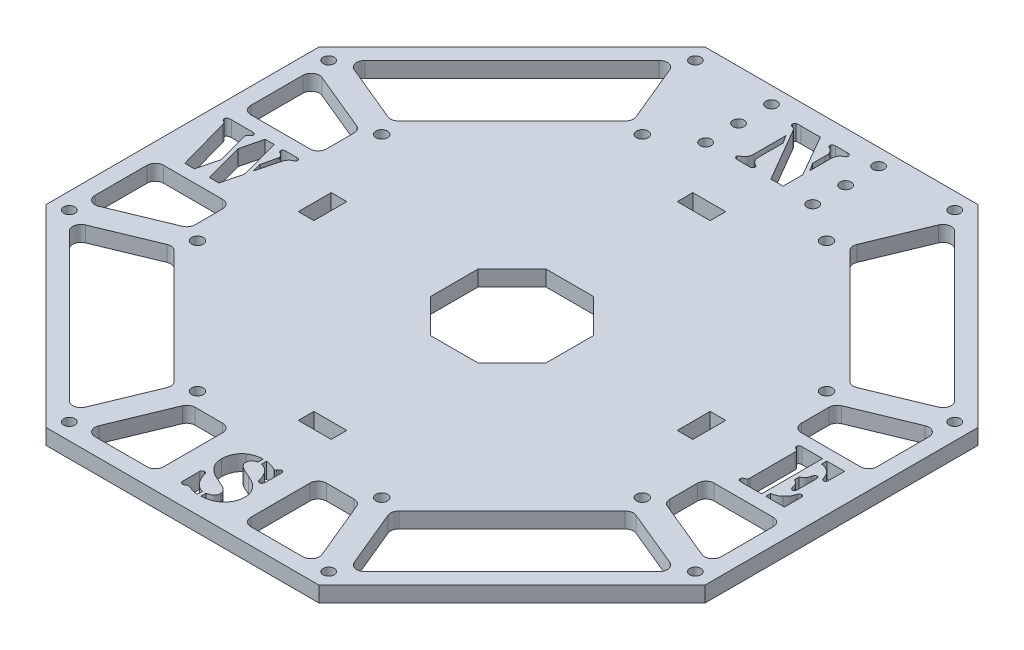
SolidWorks part; units mm, degrees
material "Custom Plastic"
ref_plane "Front Plane" through (0, 0, 0) normal (0, 0, 1) x (1, 0, 0)
ref_plane "Top Plane" through (0, 0, 0) normal (0, 1, 0) x (1, 0, 0)
ref_plane "Right Plane" through (0, 0, 0) normal (1, 0, 0) x (0, 0, -1)
ref_axis "Axis1" through (0, -0.2997, 0) along (0, 1, 0)
sketch "Base sketch" plane through (0, 0, 0) normal (0, 1, 0) x (1, 0, 0)
  line L1 (-127, 52.6051) -> (-127, -52.6051)
  line L2 (-127, -52.6051) -> (-52.6051, -127)
  line L3 (-52.6051, -127) -> (52.6051, -127)
  line L4 (52.6051, -127) -> (127, -52.6051)
  line L5 (127, -52.6051) -> (127, 52.6051)
  line L6 (127, 52.6051) -> (52.6051, 127)
  line L7 (52.6051, 127) -> (-52.6051, 127)
  line L8 (-52.6051, 127) -> (-127, 52.6051)
  circle A0 centre (0, 0) radius 127 construction
  dimension "D1" = 254
extrude "Base" add sketch "Base sketch" along normal blind 6
sketch "Sketch4" plane through (0, 6, 0) normal (0, 1, 0) x (1, 0, 0)
  line L0 (0, 0) -> (0, 127) construction
  line L1 (52.6051, 127) -> (-52.6051, 127) construction
  line L4 (-6.35, 70.025) -> (6.35, 70.025)
  line L5 (-6.35, 70.025) -> (-6.35, 76.025)
  line L6 (-6.35, 76.025) -> (6.35, 76.025)
  line L7 (6.35, 70.025) -> (6.35, 76.025)
  line L8 (-6.35, 70.025) -> (6.35, 76.025) construction
  line L10 (-6.35, 76.025) -> (6.35, 70.025) construction
  point P5 (0, 73.025)
  dimension "D1" = 6
  dimension "D2" = 12.7
  dimension "D3" = 53.975
extrude "Support cutouts" cut sketch "Sketch4" against normal up to next
pattern_circular "Support cutout pattern" count 4 over 360 about axis through (0, -0.2997, 0) along (0, 1, 0) of "Support cutouts"
sketch "Sketch11" plane through (0, 6, 0) normal (0, 1, 0) x (1, 0, 0)
  line L1 (92.075, 38.1387) -> (38.1387, 92.075) construction
  line L2 (38.1387, 92.075) -> (-38.1387, 92.075) construction
  line L3 (-38.1387, 92.075) -> (-92.075, 38.1387) construction
  line L4 (-92.075, 38.1387) -> (-92.075, -38.1387) construction
  line L5 (-92.075, -38.1387) -> (-38.1387, -92.075) construction
  line L6 (-38.1387, -92.075) -> (38.1387, -92.075) construction
  line L7 (38.1387, -92.075) -> (92.075, -38.1387) construction
  line L8 (92.075, -38.1387) -> (92.075, 38.1387) construction
  line L9 (-35.5085, 85.725) -> (-85.725, 35.5085)
  line L10 (-85.725, 35.5085) -> (-85.725, -35.5085)
  line L11 (-85.725, -35.5085) -> (-35.5085, -85.725)
  line L12 (-35.5085, -85.725) -> (35.5085, -85.725)
  line L13 (35.5085, -85.725) -> (85.725, -35.5085)
  line L14 (85.725, -35.5085) -> (85.725, 35.5085)
  line L15 (85.725, 35.5085) -> (35.5085, 85.725)
  line L16 (35.5085, 85.725) -> (-35.5085, 85.725)
  circle A0 centre (0, 0) radius 92.075 construction
  circle A1 centre (0, 0) radius 85.725 construction
  dimension "D1" = 184.15
  dimension "D2" = 6.35
hole_wizard "#8 Clearance Hole1" positions "Sketch13" profile "Sketch12" hole size "#8" standard "ANSI Inch" end condition through all
sketch "Sketch13" plane through (0, 6, 0) normal (0, 1, 0) x (1, 0, 0)
  point P0 (-85.725, 35.5085)
  point P3 (-35.5085, 85.725)
  point P6 (35.5085, 85.725)
  point P9 (85.725, 35.5085)
  point P12 (85.725, -35.5085)
  point P15 (35.5085, -85.725)
  point P18 (-35.5085, -85.725)
  point P21 (-85.725, -35.5085)
sketch "Sketch12" plane through (-85.725, 6, -35.5085) normal (1, 0, 0) x (0, 0, 1)
  line L0 (0, 0) -> (0, 6)
  line L1 (0, 6) -> (2.2479, 6)
  line L2 (2.2479, 6) -> (2.2479, 0)
  line L5 (2.2479, 0) -> (0, 0)
  line L11 (0, -6.35) -> (0, 107.95) construction
  dimension "Thru Hole Dia." = 4.4958
  dimension "Thru Hole Depth" = 6
sketch "Sketch29" plane through (0, 6, 0) normal (0, 1, 0) x (1, 0, 0)
  line L0 (-6.35, 70.025) -> (6.35, 70.025) construction
  line L1 (-22.225, -9.2059) -> (-9.2059, -22.225)
  line L2 (-9.2059, -22.225) -> (9.2059, -22.225)
  line L3 (9.2059, -22.225) -> (22.225, -9.2059)
  line L4 (22.225, -9.2059) -> (22.225, 9.2059)
  line L5 (22.225, 9.2059) -> (9.2059, 22.225)
  line L6 (9.2059, 22.225) -> (-9.2059, 22.225)
  line L7 (-9.2059, 22.225) -> (-22.225, 9.2059)
  line L8 (-22.225, 9.2059) -> (-22.225, -9.2059)
  circle A0 centre (0, 0) radius 22.225 construction
  dimension "D1" = 44.45
extrude "Motor wire holes" cut sketch "Sketch29" against normal through all
sketch "mount sketch" plane through (0, 6, 0) normal (0, 1, 0) x (1, 0, 0)
  line L0 (52.6051, 127) -> (-52.6051, 127) construction
  line L1 (49.9749, 120.65) -> (-49.9749, 120.65) construction
  line L2 (-49.9749, 120.65) -> (-120.65, 49.9749) construction
  line L3 (-120.65, 49.9749) -> (-120.65, -49.9749) construction
  line L4 (-120.65, -49.9749) -> (-49.9749, -120.65) construction
  line L5 (-49.9749, -120.65) -> (49.9749, -120.65) construction
  line L6 (49.9749, -120.65) -> (120.65, -49.9749) construction
  line L7 (120.65, -49.9749) -> (120.65, 49.9749) construction
  line L8 (120.65, 49.9749) -> (49.9749, 120.65) construction
  circle A0 centre (0, 0) radius 120.65 construction
  dimension "D1" = 6.35
hole_wizard "mount clearance holes" positions "Sketch32" profile "Sketch31" hole size "#8" standard "ANSI Inch"
sketch "Sketch32" plane through (0, 6, 0) normal (0, 1, 0) x (1, 0, 0)
  point P0 (-120.65, 49.9749)
  point P3 (-49.9749, 120.65)
  point P6 (49.9749, 120.65)
  point P9 (120.65, 49.9749)
  point P12 (120.65, -49.9749)
  point P15 (49.9749, -120.65)
  point P18 (-49.9749, -120.65)
  point P21 (-120.65, -49.9749)
sketch "Sketch31" plane through (-120.65, 6, -49.9749) normal (1, 0, 0) x (0, 0, 1)
  line L0 (0, 0) -> (0, 6.35)
  line L1 (0, 6.35) -> (2.1526, 6.35)
  line L2 (2.1526, 6.35) -> (2.1526, 0)
  line L5 (2.1526, 0) -> (0, 0)
  line L10 (0, 6.35) -> (-2.1526, 6.35) construction
  line L11 (0, -6.35) -> (0, 107.95) construction
  dimension "Hole Dia." = 4.3053
  dimension "Hole Depth" = 6.35
  dimension "Drill Angle" = 180
sketch "Sketch33" plane through (0, 6, 0) normal (0, 1, 0) x (1, 0, 0)
  line L0 (0, 0) -> (0, 95.25) construction
  line L1 (127, -52.6051) -> (127, 52.6051) construction
  line L2 (-20.6375, 120.65) -> (20.6375, 120.65) construction
  line L3 (0, 95.25) -> (0, 107.95) construction
  line L4 (-20.6375, 107.95) -> (20.6375, 107.95) construction
  line L5 (0, 107.95) -> (0, 120.65) construction
  line L6 (-20.6375, 95.25) -> (20.6375, 95.25) construction
  line L7 (52.6051, 127) -> (-52.6051, 127) construction
  line L9 (20.6375, 95.25) -> (20.6375, 107.95) construction
  line L10 (20.6375, 107.95) -> (20.6375, 120.65) construction
  line L11 (-20.6375, 95.25) -> (-20.6375, 107.95) construction
  line L12 (-20.6375, 107.95) -> (-20.6375, 120.65) construction
  dimension "D1" = 6.35
  dimension "D2" = 12.7
  dimension "D3" = 41.275
hole_wizard "#8 Clearance Hole2" positions "Sketch35" profile "Sketch34" hole size "#8" standard "ANSI Inch" end condition through all
sketch "Sketch35" plane through (0, 6, 0) normal (0, 1, 0) x (1, 0, 0)
  point P0 (20.6375, 95.25)
  point P3 (20.6375, 107.95)
  point P6 (20.6375, 120.65)
  point P9 (-20.6375, 120.65)
  point P12 (-20.6375, 107.95)
  point P15 (-20.6375, 95.25)
sketch "Sketch34" plane through (20.6375, 6, -95.25) normal (1, 0, 0) x (0, 0, 1)
  line L0 (0, 0) -> (0, 6)
  line L1 (0, 6) -> (2.1526, 6)
  line L2 (2.1526, 6) -> (2.1526, 0)
  line L5 (2.1526, 0) -> (0, 0)
  line L11 (0, -6.35) -> (0, 107.95) construction
  dimension "Thru Hole Dia." = 4.3053
  dimension "Thru Hole Depth" = 6
sketch "Sketch36" plane through (0, 6, 0) normal (0, 1, 0) x (1, 0, 0)
  line L0 (-15.7154, 15.7154) -> (-89.8026, 89.8026) construction
  line L1 (-9.2059, 22.225) -> (-22.225, 9.2059) construction
  line L2 (-52.6051, 127) -> (-127, 52.6051) construction
  line L3 (-112.6149, 51.8015) -> (-90.3899, 42.5956)
  line L4 (-86.9298, 43.2839) -> (-43.2839, 86.9298)
  line L5 (-113.645, 56.9799) -> (-56.9799, 113.645)
  line L6 (-120.65, 49.9749) -> (-85.725, 35.5085) construction
  line L7 (-51.8015, 112.6149) -> (-42.5956, 90.3899)
  line L8 (56.9799, 113.645) -> (113.645, 56.9799)
  line L9 (112.6149, 51.8015) -> (90.3899, 42.5956)
  line L10 (43.2839, 86.9298) -> (86.9298, 43.2839)
  line L11 (51.8015, 112.6149) -> (42.5956, 90.3899)
  line L12 (113.645, -56.9799) -> (56.9799, -113.645)
  line L13 (51.8015, -112.6149) -> (42.5956, -90.3899)
  line L14 (86.9298, -43.2839) -> (43.2839, -86.9298)
  line L15 (112.6149, -51.8015) -> (90.3899, -42.5956)
  line L16 (-56.9799, -113.645) -> (-113.645, -56.9799)
  line L17 (-112.6149, -51.8015) -> (-90.3899, -42.5956)
  line L18 (-43.2839, -86.9298) -> (-86.9298, -43.2839)
  line L19 (-51.8015, -112.6149) -> (-42.5956, -90.3899)
  line L20 (127, 52.6051) -> (52.6051, 127) construction
  line L21 (0, 0) -> (65.1069, 65.1069) construction
  line L22 (-15.7154, 15.7154) -> (0, 0) construction
  circle A1 centre (-85.725, 35.5085) radius 2.2479 construction
  arc A2 (-112.6149, 51.8015) -> (-113.645, 56.9799) centre (-111.3999, 54.7348) cw
  arc A3 (-90.3899, 42.5956) -> (-86.9298, 43.2839) centre (-89.1749, 45.5289) ccw
  arc A4 (-42.5956, 90.3899) -> (-43.2839, 86.9298) centre (-45.5289, 89.1749) cw
  arc A5 (-51.8015, 112.6149) -> (-56.9799, 113.645) centre (-54.7348, 111.3999) ccw
  arc A6 (112.6149, 51.8015) -> (113.645, 56.9799) centre (111.3999, 54.7348) ccw
  arc A7 (90.3899, 42.5956) -> (86.9298, 43.2839) centre (89.1749, 45.5289) cw
  arc A8 (42.5956, 90.3899) -> (43.2839, 86.9298) centre (45.5289, 89.1749) ccw
  arc A9 (51.8015, 112.6149) -> (56.9799, 113.645) centre (54.7348, 111.3999) cw
  arc A10 (51.8015, -112.6149) -> (56.9799, -113.645) centre (54.7348, -111.3999) ccw
  arc A11 (42.5956, -90.3899) -> (43.2839, -86.9298) centre (45.5289, -89.1749) cw
  arc A12 (90.3899, -42.5956) -> (86.9298, -43.2839) centre (89.1749, -45.5289) ccw
  arc A13 (112.6149, -51.8015) -> (113.645, -56.9799) centre (111.3999, -54.7348) cw
  arc A14 (-112.6149, -51.8015) -> (-113.645, -56.9799) centre (-111.3999, -54.7348) ccw
  arc A15 (-90.3899, -42.5956) -> (-86.9298, -43.2839) centre (-89.1749, -45.5289) cw
  arc A16 (-42.5956, -90.3899) -> (-43.2839, -86.9298) centre (-45.5289, -89.1749) ccw
  arc A17 (-51.8015, -112.6149) -> (-56.9799, -113.645) centre (-54.7348, -111.3999) cw
  point P17 (-85.3124, 85.3124)
  point P18 (-65.1069, 65.1069)
  point P20 (-117.0049, 53.6199)
  point P23 (-88.4299, 41.7838)
  point P26 (-41.7838, 88.4299)
  point P29 (-53.6199, 117.0049)
  point P69 (0, 0)
  dimension "D2" = 6.35
  dimension "D4" = 3.175
  dimension "D1" = 6.35
  dimension "D3" = 9.525
  dimension "D6" = 6.35
  dimension "D5" = 4
extrude "Lightenning 1" cut sketch "Sketch36" against normal through all
sketch "Sketch37" plane through (0, 6, 0) normal (0, 1, 0) x (1, 0, 0)
  text T0 "N" font "Stencil" height in points 100
  text T1 "S" font "Stencil" height in points 100
  text T2 "E" font "Stencil" height in points 100
  text T3 "W" font "Stencil" height in points 100
extrude "Directions" cut sketch "Sketch37" against normal through all
sketch "Sketch38" plane through (0, 6, 0) normal (0, 1, 0) x (1, 0, 0)
  line L0 (120.65, 40.0683) -> (120.65, 20.0025)
  line L1 (117.475, 16.8275) -> (94.7002, 16.8275)
  line L2 (91.5252, 20.0025) -> (91.5252, 30.6346)
  line L3 (93.4852, 33.5679) -> (116.26, 43.0016)
  line L4 (85.725, 35.5085) -> (120.65, 49.9749) construction
  line L5 (0, 0) -> (127, 0) construction
  line L6 (127, -52.6051) -> (127, 52.6051) construction
  line L7 (101.5024, 47.1986) -> (103.1875, 42.7417) construction
  line L8 (90.3899, 42.5956) -> (112.6149, 51.8015) construction
  line L9 (103.1875, 42.7417) -> (104.8726, 38.2848) construction
  line L10 (113.645, 56.9799) -> (120.65, 49.9749) construction
  line L11 (120.65, 49.9749) -> (120.65, 44.82) construction
  line L12 (113.645, 56.9799) -> (56.9799, 113.645) construction
  line L14 (117.475, -16.8275) -> (94.7002, -16.8275)
  line L15 (120.65, -40.0683) -> (120.65, -20.0025)
  line L16 (93.4852, -33.5679) -> (116.26, -43.0016)
  line L17 (91.5252, -20.0025) -> (91.5252, -30.6346)
  arc A0 (117.475, -16.8275) -> (120.65, -20.0025) centre (117.475, -20.0025) cw
  arc A1 (94.7002, -16.8275) -> (91.5252, -20.0025) centre (94.7002, -20.0025) ccw
  arc A2 (93.4852, -33.5679) -> (91.5252, -30.6346) centre (94.7002, -30.6346) cw
  arc A3 (120.65, -40.0683) -> (116.26, -43.0016) centre (117.475, -40.0683) cw
  arc A4 (120.65, 20.0025) -> (117.475, 16.8275) centre (117.475, 20.0025) cw
  arc A5 (94.7002, 16.8275) -> (91.5252, 20.0025) centre (94.7002, 20.0025) cw
  arc A6 (91.5252, 30.6346) -> (93.4852, 33.5679) centre (94.7002, 30.6346) cw
  arc A7 (120.65, 40.0683) -> (116.26, 43.0016) centre (117.475, 40.0683) ccw
  arc A8 (112.6149, 51.8015) -> (113.645, 56.9799) centre (111.3999, 54.7348) ccw construction
  point P28 (120.65, -16.8275)
  point P31 (91.5252, -16.8275)
  point P34 (91.5252, -32.7561)
  point P37 (120.65, -44.82)
  point P40 (120.65, 16.8275)
  point P43 (91.5252, 16.8275)
  point P46 (91.5252, 32.7561)
  dimension "D1" = 33.655
extrude "Lightenning 2" cut sketch "Sketch38" against normal through all
pattern_circular "Lightenning 2 circ pat" count 3 every 90 about axis through (0, -0.2997, 0) along (0, 1, 0) of "Lightenning 2" reverse direction yes
equation "\"MAT_THICKNESS\"=0.23622"
equation "\"D1@Base\"=\"MAT_THICKNESS\""
equation "\"D1@Sketch4\"=\"MAT_THICKNESS\""
